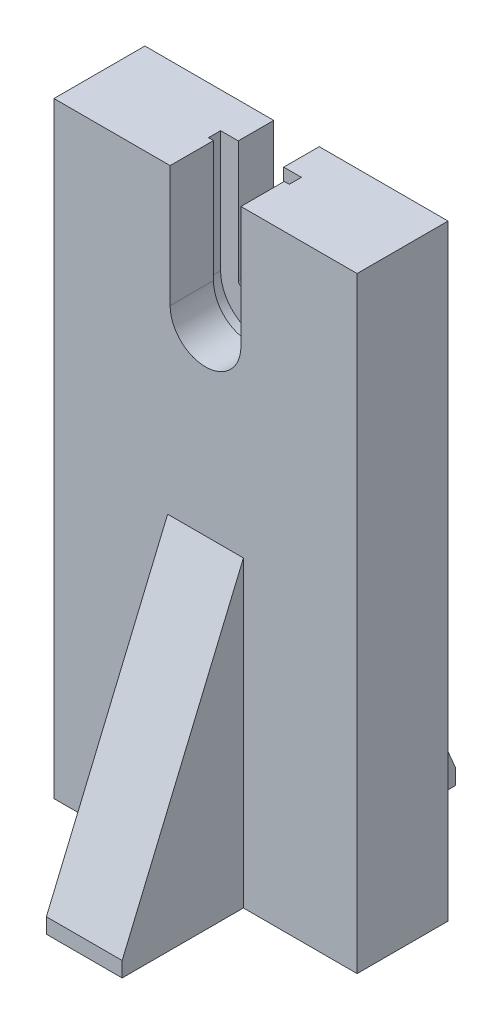
SolidWorks part; units mm, degrees
ref_plane "Front Plane" through (0, 0, 0) normal (0, 0, 1) x (1, 0, 0)
ref_plane "Top Plane" through (0, 0, 0) normal (0, 1, 0) x (1, 0, 0)
ref_plane "Right Plane" through (0, 0, 0) normal (1, 0, 0) x (0, 0, -1)
sketch "Sketch1" plane through (0, 0, 0) normal (0, 0, 1) x (1, 0, 0)
  line L1 (0, 0) -> (20, 0)
  line L2 (0, 0) -> (0, 40)
  line L3 (0, 40) -> (20, 40)
  line L4 (20, 0) -> (20, 40)
  dimension "D1" = 40
  dimension "D2" = 20
extrude "Boss-Extrude1" add sketch "Sketch1" along normal blind 6
sketch "Sketch2" plane through (0, 40, 0) normal (0, 1, 0) x (1, 0, 0)
  line L1 (12.665, -2.34) -> (12.665, -3.14)
  line L2 (12.665, -3.14) -> (12.335, -3.14)
  line L3 (12.335, -3.14) -> (12.335, -6)
  line L4 (20, -6) -> (0, -6) construction
  line L5 (12.335, -6) -> (7.665, -6)
  line L6 (7.665, -6) -> (7.665, -3.14)
  line L7 (7.665, -3.14) -> (7.335, -3.14)
  line L8 (7.335, -3.14) -> (7.335, -2.34)
  line L9 (7.335, -2.34) -> (8.5, -2.34)
  line L10 (8.5, -2.34) -> (8.5, 0)
  line L11 (20, 0) -> (0, 0) construction
  line L12 (8.5, 0) -> (11.5, 0)
  line L13 (11.5, 0) -> (11.5, -2.34)
  line L14 (11.5, -2.34) -> (12.665, -2.34)
  point P2 (10, 0)
  point P17 (10, 0)
  point P18 (7.335, -2.74)
  point P19 (12.665, -2.74)
  dimension "D1" = 3
  dimension "D2" = 4.67
  dimension "D3" = 5.33
  dimension "D4" = 0.8
  dimension "D5" = 3.66
extrude "Cut-Extrude1" cut sketch "Sketch2" against normal blind 8
sketch "Sketch3" plane through (0, 0, 6) normal (0, 0, 1) x (1, 0, 0)
  line L2 (7.665, 32) -> (12.335, 32)
  arc A0 (7.665, 32) -> (12.335, 32) centre (10, 32) ccw
  point P3 (10, 32.461)
  point P6 (10, 32)
extrude "Cut-Extrude2" cut sketch "Sketch3" against normal blind 2.86
sketch "Sketch5" plane through (0, 0, 3.14) normal (0, 0, 1) x (1, 0, 0)
  line L1 (7.335, 32) -> (12.665, 32)
  line L2 (12.665, 32) -> (11.5, 32) construction
  arc A0 (7.335, 32) -> (12.665, 32) centre (10, 32) ccw
  point P1 (10, 32)
extrude "Cut-Extrude3" cut sketch "Sketch5" against normal blind 0.8
sketch "Sketch6" plane through (0, 0, 2.34) normal (0, 0, 1) x (1, 0, 0)
  circle A0 centre (10, 32) radius 1.27
  circle A1 centre (10, 30.73) radius 0.23
  circle A2 centre (8.73, 32) radius 0.23
  circle A3 centre (10, 33.27) radius 0.23
  circle A4 centre (11.27, 32) radius 0.23
  dimension "D1" = 2.54
  dimension "D2" = 0.46
  dimension "D3" = 4
sketch "Sketch7" plane through (0, 0, 2.34) normal (0, 0, 1) x (1, 0, 0)
  line L0 (11.5, 32) -> (8.5, 32) construction
  line L1 (9.77, 30.73) -> (9.77, 32)
  line L2 (10.23, 32) -> (10.23, 30.73)
  line L3 (8.5, 32) -> (8.96, 32)
  line L4 (9.77, 32) -> (10.23, 32)
  line L5 (11.04, 32) -> (11.5, 32)
  arc A0 (8.5, 32) -> (8.96, 32) centre (8.73, 32) ccw
  circle A1 centre (8.73, 32) radius 0.23 construction
  arc A2 (11.04, 32) -> (11.5, 32) centre (11.27, 32) ccw
  circle A3 centre (11.27, 32) radius 0.23 construction
  arc A4 (9.77, 30.73) -> (10.23, 30.73) centre (10, 30.73) ccw
  circle A5 centre (10, 30.73) radius 0.23 construction
extrude "Cut-Extrude4" cut sketch "Sketch7" against normal through all
sketch "Sketch8" plane through (0, 0, 0) normal (0, -1, 0) x (1, 0, 0)
  line L1 (7.5, 0) -> (12.5, 0)
  line L2 (7.5, 0) -> (7.5, -8)
  line L3 (7.5, -8) -> (12.5, -8)
  line L4 (12.5, 0) -> (12.5, -8)
  line L6 (0, 0) -> (20, 0) construction
  dimension "D1" = 8
  dimension "D2" = 5
ref_plane "Plane1" through (10, 0, 0) normal (1, 0, 0) x (0, 0, -1)
extrude "Boss-Extrude2" add sketch "Sketch8" against normal blind 1
sketch "Sketch9" plane through (10, 0, 0) normal (1, 0, 0) x (0, 0, -1)
  line L0 (8, 1) -> (0, 20)
  line L3 (0, 0) -> (0, 40) construction
  point P2 (8, 1)
  point P8 (8, 0)
  point P9 (8, 0)
  point P12 (0, 0)
rib "Rib2" sketch "Sketch9" sketch "Sketch9" thickness 5 extrusion direction parallel to sketch draft on no parameters "D1"=5
ref_plane "Plane2" through (0, 0, 3) normal (0, 0, 1) x (1, 0, 0)
mirror "Mirror1" about plane through (0, 0, 3) normal (0, 0, 1) of "Rib2", "Boss-Extrude2"
shell "Shell1" thickness 1 removed face at (10, 0, 3)
equation "\"D1@Cut-Extrude2\"= 3.66 - 0.8"
equation "\"D1@Cut-Extrude3\"= 0.8"
